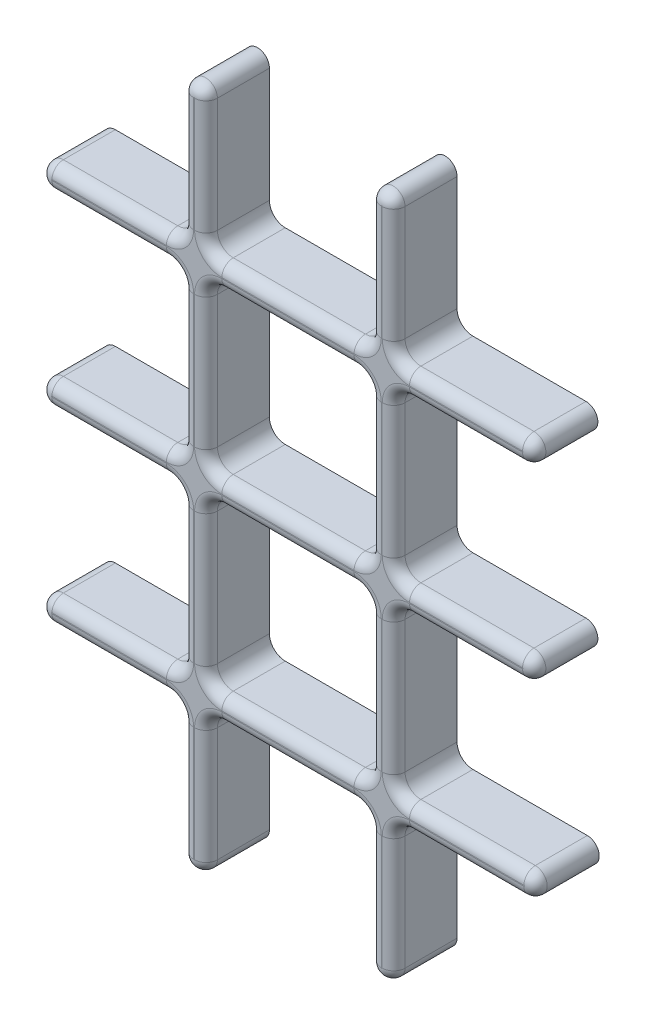
SolidWorks part; units mm, degrees
material "Nylon 101"
ref_plane "Front Plane" through (0, 0, 0) normal (0, 0, 1) x (1, 0, 0)
ref_plane "Top Plane" through (0, 0, 0) normal (0, 1, 0) x (1, 0, 0)
ref_plane "Right Plane" through (0, 0, 0) normal (1, 0, 0) x (0, 0, -1)
sketch "Sketch1" plane through (0, 0, 0) normal (0, 0, 1) x (1, 0, 0)
  line L0 (57.4675, -133.9692) -> (7.8105, -133.9692)
  line L2 (57.3334, -115.1732) -> (7.8105, -115.1732)
  line L4 (57.3334, -96.3772) -> (7.8105, -96.3772)
  line L5 (23.241, -80.9467) -> (23.241, -149.3997)
  line L7 (42.037, -149.3997) -> (42.037, -80.9467)
  arc A0 (56.1975, -135.2392) -> (56.1975, -132.6992) centre (56.1975, -133.9692) ccw construction
  arc A1 (9.0805, -132.6992) -> (9.0805, -135.2392) centre (9.0805, -133.9692) ccw construction
  arc A2 (9.0805, -113.9032) -> (9.0805, -116.4432) centre (9.0805, -115.1732) ccw construction
  arc A3 (9.0805, -95.1072) -> (9.0805, -97.6472) centre (9.0805, -96.3772) ccw construction
  arc A4 (24.511, -82.2167) -> (21.971, -82.2167) centre (23.241, -82.2167) ccw construction
  arc A5 (21.971, -148.1297) -> (24.511, -148.1297) centre (23.241, -148.1297) ccw construction
  arc A6 (40.767, -148.1297) -> (43.307, -148.1297) centre (42.037, -148.1297) ccw construction
  arc A7 (43.307, -82.2167) -> (40.767, -82.2167) centre (42.037, -82.2167) ccw construction
extrude "Extrude-Thin1" add sketch "Sketch1" along normal blind 6.35 thin thin type mid plane wall 2.3813
combine bodies "Combine1" operation type add bodies to combine 101 102 103 104 105
fillet "Fillet1" radius 1.5875 24 edges at (40.8464, -97.5679, 3.175) (40.8464, -95.1866, 3.175) (43.2276, -97.5679, 3.175) (43.2276, -95.1866, 3.175) (24.4316, -97.5679, 3.175) (22.0504, -97.5679, 3.175) (24.4316, -95.1866, 3.175) (22.0504, -95.1866, 3.175) (43.2276, -116.3639, 3.175) (43.2276, -113.9826, 3.175) (40.8464, -116.3639, 3.175) (40.8464, -113.9826, 3.175) (24.4316, -116.3639, 3.175) (24.4316, -113.9826, 3.175) (22.0504, -116.3639, 3.175) (22.0504, -113.9826, 3.175) (22.0504, -135.1599, 3.175) (22.0504, -132.7786, 3.175) (24.4316, -135.1599, 3.175) (24.4316, -132.7786, 3.175) (43.2276, -132.7786, 3.175) (40.8464, -135.1599, 3.175) (40.8464, -132.7786, 3.175) (43.2276, -135.1599, 3.175)
fillet "Fillet2" 2 edges at (7.8105, -135.1599, 3.175) (7.8105, -132.7786, 3.175) type full round first side face at (14.1367, -135.1599, 3.175) second side face at (14.1367, -132.7786, 3.175) middle face at (7.8105, -133.9692, 3.175)
fillet "Fillet3" 2 edges at (7.8105, -116.3639, 3.175) (7.8105, -113.9826, 3.175) type full round first side face at (14.1367, -116.3639, 3.175) second side face at (14.1367, -113.9826, 3.175) middle face at (7.8105, -115.1732, 3.175)
fillet "Fillet4" 2 edges at (7.8105, -97.5679, 3.175) (7.8105, -95.1866, 3.175) type full round first side face at (14.1367, -97.5679, 3.175) second side face at (14.1367, -95.1866, 3.175) middle face at (7.8105, -96.3772, 3.175)
fillet "Fillet5" 2 edges at (22.0504, -80.9467, 3.175) (24.4316, -80.9467, 3.175) type full round first side face at (22.0504, -87.2729, 3.175) second side face at (24.4316, -87.2729, 3.175) middle face at (23.241, -80.9467, 3.175)
fillet "Fillet6" 2 edges at (40.8464, -80.9467, 3.175) (43.2276, -80.9467, 3.175) type full round first side face at (40.8464, -87.2729, 3.175) second side face at (43.2276, -87.2729, 3.175) middle face at (42.037, -80.9467, 3.175)
fillet "Fillet7" 2 edges at (57.3334, -95.1866, 3.175) (57.3334, -97.5679, 3.175) type full round first side face at (51.0743, -95.1866, 3.175) second side face at (51.0743, -97.5679, 3.175) middle face at (57.3334, -96.3772, 3.175)
fillet "Fillet8" 2 edges at (57.3334, -113.9826, 3.175) (57.3334, -116.3639, 3.175) type full round first side face at (51.0743, -113.9826, 3.175) second side face at (51.0743, -116.3639, 3.175) middle face at (57.3334, -115.1732, 3.175)
fillet "Fillet10" 2 edges at (57.4675, -132.7786, 3.175) (57.4675, -135.1599, 3.175) type full round first side face at (51.1413, -132.7786, 3.175) second side face at (51.1413, -135.1599, 3.175) middle face at (57.4675, -133.9692, 3.175)
fillet "Fillet11" 2 edges at (43.2276, -149.3997, 3.175) (40.8464, -149.3997, 3.175) type full round first side face at (43.2276, -143.0735, 3.175) second side face at (40.8464, -143.0735, 3.175) middle face at (42.037, -149.3997, 3.175)
fillet "Fillet12" 2 edges at (22.0504, -149.3997, 3.175) (24.4316, -149.3997, 3.175) type full round first side face at (22.0504, -143.0735, 3.175) second side face at (24.4316, -143.0735, 3.175) middle face at (23.241, -149.3997, 3.175)
fillet "Fillet13" radius 1.143 68 edges at (40.3814, -98.0328, 6.35) (32.639, -97.5679, 6.35) (24.8966, -98.0328, 6.35) (24.4316, -105.7752, 6.35) (24.8966, -113.5176, 6.35) (32.639, -113.9826, 6.35) (40.3814, -113.5176, 6.35) (40.8464, -105.7752, 6.35) (40.3814, -116.8288, 6.35) (32.639, -116.3639, 6.35) (24.8966, -116.8288, 6.35) (24.4316, -124.5712, 6.35) (24.8966, -132.3136, 6.35) (32.639, -132.7786, 6.35) (40.3814, -132.3136, 6.35) (40.8464, -124.5712, 6.35) (21.5854, -135.6248, 6.35) (14.732, -135.1599, 6.35) (7.8105, -133.9692, 6.35) (14.732, -132.7786, 6.35) (21.5854, -132.3136, 6.35) (22.0504, -124.5712, 6.35) (21.5854, -116.8288, 6.35) (14.732, -116.3639, 6.35) (7.8105, -115.1732, 6.35) (14.732, -113.9826, 6.35) (21.5854, -113.5176, 6.35) (22.0504, -105.7752, 6.35) (21.5854, -98.0328, 6.35) (14.732, -97.5679, 6.35) (7.8105, -96.3772, 6.35) (14.732, -95.1866, 6.35) (21.5854, -94.7216, 6.35) (22.0504, -87.8682, 6.35) (23.241, -80.9467, 6.35) (24.4316, -87.8682, 6.35) (24.8966, -94.7216, 6.35) (32.639, -95.1866, 6.35) (40.3814, -94.7216, 6.35) (40.8464, -87.8682, 6.35) (42.037, -80.9467, 6.35) (43.2276, -87.8682, 6.35) (43.6926, -94.7216, 6.35) (50.479, -95.1866, 6.35) (57.3334, -96.3772, 6.35) (50.479, -97.5679, 6.35) (43.6926, -98.0328, 6.35) (43.2276, -105.7752, 6.35) (43.6926, -113.5176, 6.35) (50.479, -113.9826, 6.35) (57.3334, -115.1732, 6.35) (50.479, -116.3639, 6.35) (43.6926, -116.8288, 6.35) (43.2276, -124.5712, 6.35) (43.6926, -132.3136, 6.35) (50.546, -132.7786, 6.35) (57.4675, -133.9692, 6.35) (50.546, -135.1599, 6.35) (43.6926, -135.6248, 6.35) (43.2276, -142.4782, 6.35) (42.037, -149.3997, 6.35) (40.8464, -142.4782, 6.35) (40.3814, -135.6248, 6.35) (32.639, -135.1599, 6.35) (24.8966, -135.6248, 6.35) (24.4316, -142.4782, 6.35) (23.241, -149.3997, 6.35) (22.0504, -142.4782, 6.35)
